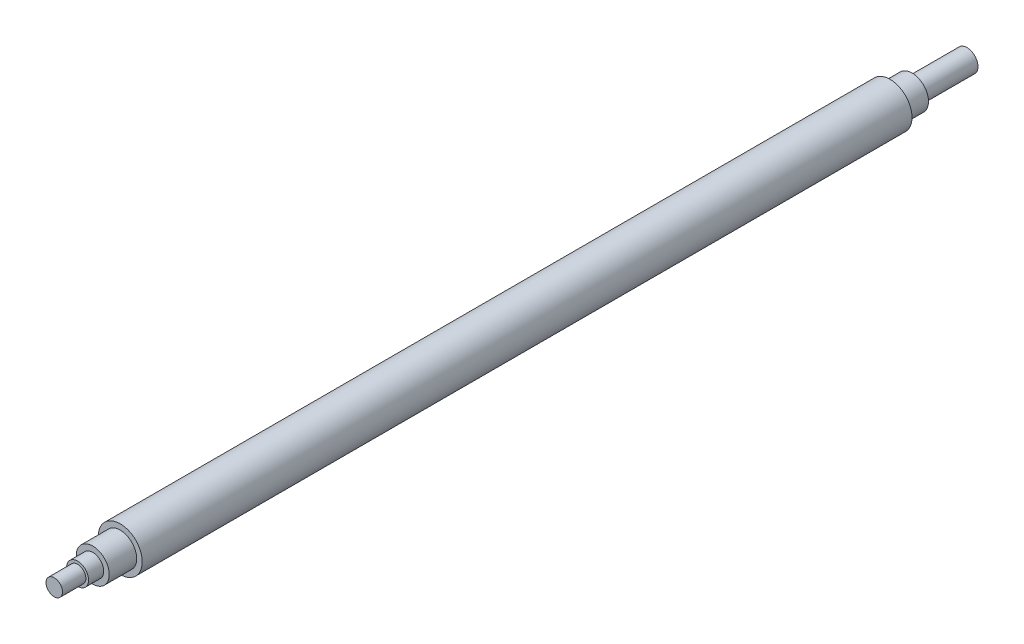
SolidWorks part; units mm, degrees
ref_plane "Piano frontale" through (0, 0, 0) normal (0, 0, 1) x (1, 0, 0)
ref_plane "Piano superiore" through (0, 0, 0) normal (0, 1, 0) x (1, 0, 0)
ref_plane "Piano destro" through (0, 0, 0) normal (1, 0, 0) x (0, 0, -1)
sketch "Schizzo2" plane through (0, 0, 0) normal (1, 0, 0) x (0, 0, -1)
  line L0 (0, 0) -> (0, 3)
  line L1 (0, 3) -> (8.5, 3)
  line L2 (8.5, 3) -> (8.5, 4)
  line L3 (8.5, 4) -> (14, 4)
  line L4 (14, 4) -> (14, 6)
  line L5 (14, 6) -> (24, 6)
  line L6 (24, 6) -> (24, 8)
  line L7 (24, 8) -> (304, 8)
  line L8 (304, 8) -> (304, 6)
  line L9 (304, 6) -> (312, 6)
  line L10 (312, 6) -> (312, 4)
  line L11 (332, 0) -> (0, 0)
  line L14 (332, 0) -> (332, 4)
  line L15 (0, 0) -> (351.0218, 0) construction
  line L18 (312, 4) -> (332, 4)
  point P33 (0, 0)
  dimension "D2" = 6
  dimension "D3" = 8
  dimension "D4" = 12
  dimension "D5" = 16
  dimension "D6" = 12
  dimension "D7" = 8
  dimension "D8" = 8.5
  dimension "D9" = 5.5
  dimension "D10" = 10
  dimension "D11" = 280
  dimension "D12" = 8
  dimension "D13" = 20
revolve "Rivoluzione2" add sketch "Schizzo2" angle 360 about L15
